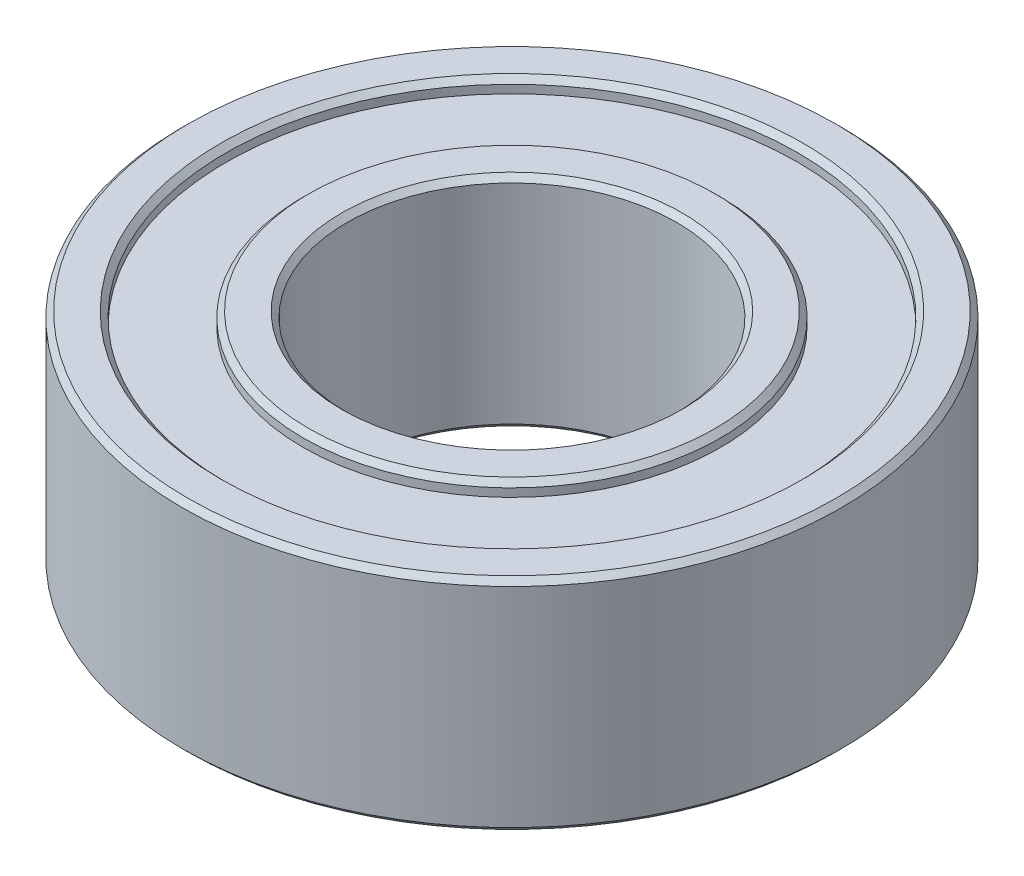
SolidWorks part; units mm, degrees
material "1023 Carbon Steel Sheet (SS)"
ref_plane "Front Plane" through (0, 0, 0) normal (0, 0, 1) x (1, 0, 0)
ref_plane "Top Plane" through (0, 0, 0) normal (0, 1, 0) x (1, 0, 0)
ref_plane "Right Plane" through (0, 0, 0) normal (1, 0, 0) x (0, 0, -1)
sketch "Sketch1" plane through (0, 0, 0) normal (0, 1, 0) x (1, 0, 0)
  circle A0 centre (0, 0) radius 6
  circle A1 centre (0, 0) radius 3
  circle A2 centre (0, 0) radius 3.8
  circle A3 centre (0, 0) radius 5.2
  dimension "D3" = 6
  dimension "D4" = 12
  dimension "D1" = 0.8
  dimension "D2" = 0.8
extrude "Boss-Extrude1" add sketch "Sketch1" along normal mid plane 4 contours A0 A3 | A2 A1 region at (-5.8303, 0, 0) region at (-3.6925, 0, 0)
extrude "Boss-Extrude2" add sketch "Sketch1<3>" along normal mid plane 3.5 contours A3 A2 region at (-5.0529, 0, 0)
sketch "Sketch1<3>" plane through (0, 0, 0) normal (0, 1, 0) x (1, 0, 0) same geometry as "Sketch1"
chamfer "Chamfer2" distance 0.1 angle 45 4 edges at (0, -2, 3.8) (0, -2, 3) (0, 2, 3.8) (0, 2, 3)
chamfer "Chamfer3" distance 0.1 angle 45 4 edges at (0, 2, 5.2) (0, 2, 6) (0, -2, 5.2) (0, -2, 6)
equation "\"D1@Boss-Extrude2\"=\"D1@Boss-Extrude1\" - 0.5"
